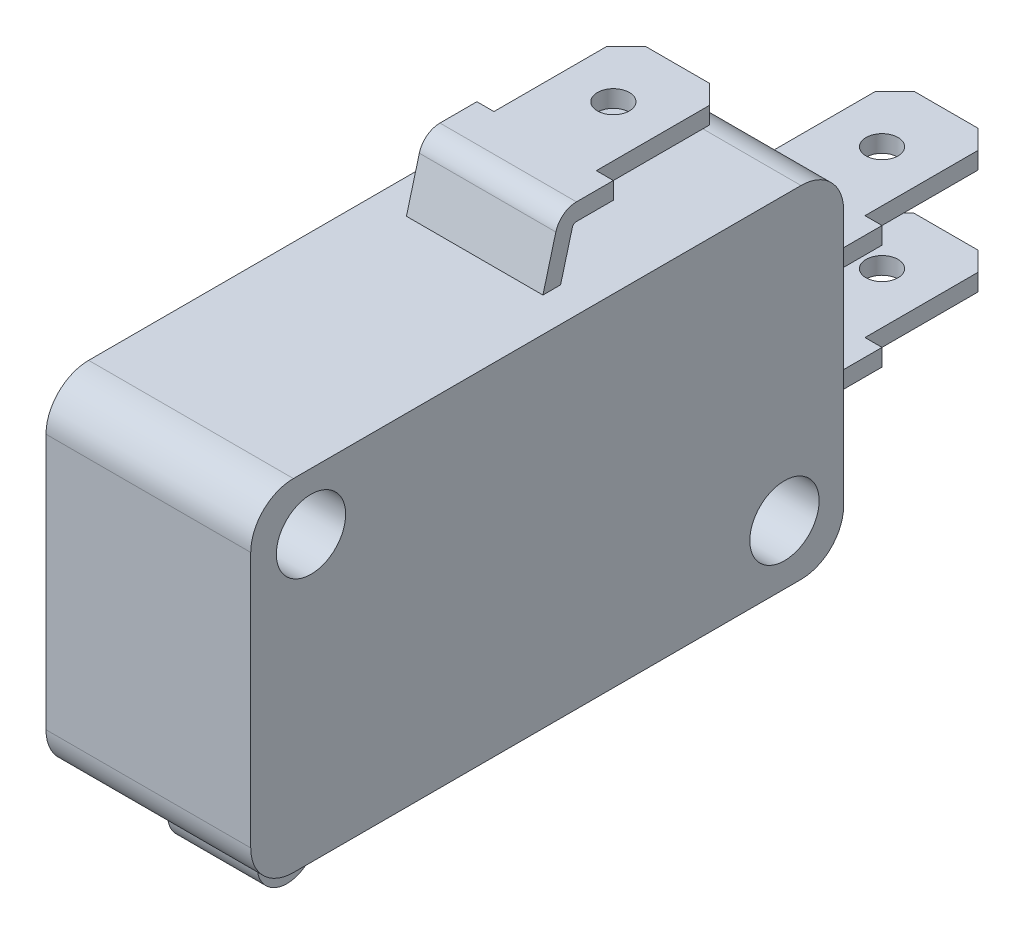
SolidWorks part; units mm, degrees
ref_plane "Alzado" through (0, 0, 0) normal (0, 0, 1) x (1, 0, 0)
ref_plane "Planta" through (0, 0, 0) normal (0, 1, 0) x (1, 0, 0)
ref_plane "Vista lateral" through (0, 0, 0) normal (1, 0, 0) x (0, 0, -1)
sketch "Croquis1" plane through (0, 0, 0) normal (1, 0, 0) x (0, 0, -1)
  line L1 (-13.9, 8) -> (13.9, 8)
  line L2 (-13.9, 8) -> (-13.9, -8)
  line L3 (-13.9, -8) -> (13.9, -8)
  line L4 (13.9, 8) -> (13.9, -8)
  line L5 (-13.9, 8) -> (13.9, -8) construction
  line L6 (-13.9, -8) -> (13.9, 8) construction
  point P0 (0, 0)
  dimension "D1" = 27.8
  dimension "D2" = 16
extrude "Saliente-Extruir1" add sketch "Croquis1" along normal mid plane 9.6
fillet "Redondeo1" radius 2 4 edges at (0, 8, 13.9) (0, 8, -13.9) (0, -8, -13.9) (0, -8, 13.9)
sketch "Croquis2" plane through (0, 0, 0) normal (0, 1, 0) x (1, 0, 0)
  line L0 (0, 0) -> (0, 22.6183) construction
  line L1 (3.2, 13.9) -> (-3.2, 13.9)
  line L2 (-4.8, 13.9) -> (4.8, 13.9) construction
  line L3 (-3.2, 13.9) -> (-3.2, 17.3)
  line L4 (-3.2, 17.3) -> (-2.4, 17.3)
  line L5 (-2.4, 17.3) -> (-2.4, 22.6)
  line L6 (-2.4, 22.6) -> (-1.5, 23.5)
  line L7 (-1.5, 23.5) -> (1.5, 23.5)
  line L8 (2.4, 22.6) -> (1.5, 23.5)
  line L9 (2.4, 17.3) -> (2.4, 22.6)
  line L10 (3.2, 17.3) -> (2.4, 17.3)
  line L11 (3.2, 13.9) -> (3.2, 17.3)
  circle A0 centre (0, 20.5) radius 0.75
  point P9 (-2.8, 17.3)
  point P14 (0, 23.5)
  point P20 (0, 13.9)
  dimension "D7" = 3
  dimension "D8" = 1.5
  dimension "D1" = 6.4
  dimension "D2" = 3.4
  dimension "D3" = 6.2
  dimension "D4" = 4.8
  dimension "D5" = 45
  dimension "D6" = 3
extrude "Saliente-Extruir2" add sketch "Croquis2" along normal blind 0.8 from offset 2.075
mirror "Simetría1" about plane through (0, 0, 0) normal (0, 1, 0) of "Saliente-Extruir2"
sketch "Croquis3" plane through (0, 0, 0) normal (1, 0, 0) x (0, 0, -1)
  line L0 (1.4, 8) -> (2.0052, 10.2588)
  line L1 (11.9, 8) -> (-11.9, 8) construction
  line L2 (2.9712, 11) -> (4.7038, 11)
  line L3 (-13.9, 6) -> (-13.9, -6) construction
  line L4 (2.2282, 8) -> (2.778, 10.0518)
  line L5 (2.9712, 10.2) -> (4.7038, 10.2)
  line L6 (4.7038, 10.2) -> (4.7038, 11)
  line L7 (1.4, 8) -> (2.2282, 8)
  line L8 (2.1727, 7.7929) -> (2.778, 10.0518) construction
  arc A0 (2.9712, 11) -> (2.0052, 10.2588) centre (2.9712, 10) ccw
  arc A1 (2.9712, 10.2) -> (2.778, 10.0518) centre (2.9712, 10) ccw
  point P10 (2.2038, 11)
  dimension "D5" = 1
  dimension "D1" = 15.3
  dimension "D2" = 3
  dimension "D3" = 2.5
  dimension "D4" = 75
  dimension "D6" = 0.8
extrude "Saliente-Extruir3" add sketch "Croquis3" along normal mid plane 6.4
sketch "Croquis4" plane through (0, 11, 0) normal (0, 1, 0) x (1, 0, 0)
  line L0 (0, 0) -> (0, 50000) construction
  line L1 (-2.4, 4.7038) -> (-2.4, 10.0038)
  line L2 (3.2, 4.7038) -> (-3.2, 4.7038) construction
  line L3 (-2.4, 10.0038) -> (-1.5, 10.9038)
  line L4 (-1.5, 10.9038) -> (1.5, 10.9038)
  line L5 (-2.4, 22.6) -> (-2.4, 17.3) construction
  line L8 (-2.4, 4.7038) -> (2.4, 4.7038)
  line L9 (2.4, 10.0038) -> (1.5, 10.9038)
  line L10 (2.4, 4.7038) -> (2.4, 10.0038)
  circle A0 centre (0, 7.9038) radius 0.75
  point P13 (0, 10.9038)
  point P15 (0, 4.7038)
  dimension "D3" = 1.5
  dimension "D4" = 3
  dimension "D1" = 45
  dimension "D2" = 6.2
extrude "Saliente-Extruir4" add sketch "Croquis4" against normal up to surface (0.8 mm away) up to face at (0, 10.2, -3.8375)
sketch "Croquis5" plane through (4.8, 0, 0) normal (1, 0, 0) x (0, 0, -1)
  line L0 (-13.9, 6) -> (-13.9, -6) construction
  line L1 (11.9, 8) -> (-11.9, 8) construction
  line L2 (13.9, -6) -> (13.9, 6) construction
  line L4 (-11.9, -8) -> (11.9, -8) construction
  circle A0 centre (-11.075, 5.325) radius 1.625
  circle A1 centre (11.125, -5.225) radius 1.625
  dimension "D1" = 3.25
  dimension "D4" = 3.25
  dimension "D6" = 1.15
  dimension "D2" = 1.2
  dimension "D3" = 1.05
  dimension "D5" = 1.15
extrude "Cortar-Extruir1" cut sketch "Croquis5" against normal through all
sketch "Croquis6" plane through (0, -8, 0) normal (0, -1, 0) x (1, 0, 0)
  line L0 (0, 0) -> (0, 17.4594) construction
  line L1 (-4.8, 13.9) -> (4.8, 13.9) construction
  line L2 (-2.1, 10.9) -> (2.1, 10.9)
  line L3 (-2.1, 10.9) -> (-2.1, 8.1)
  line L4 (-2.1, 8.1) -> (2.1, 8.1)
  line L5 (2.1, 10.9) -> (2.1, 8.1)
  line L6 (-2.1, 10.9) -> (2.1, 8.1) construction
  line L7 (-2.1, 8.1) -> (2.1, 10.9) construction
  point P3 (0, 9.5)
  dimension "D1" = 4.2
  dimension "D2" = 2.8
  dimension "D3" = 3
extrude "Saliente-Extruir5" add sketch "Croquis6" along normal blind 3
fillet "Redondeo2" radius 1.4 2 edges at (0, -11, 8.1) (0, -11, 10.9)
